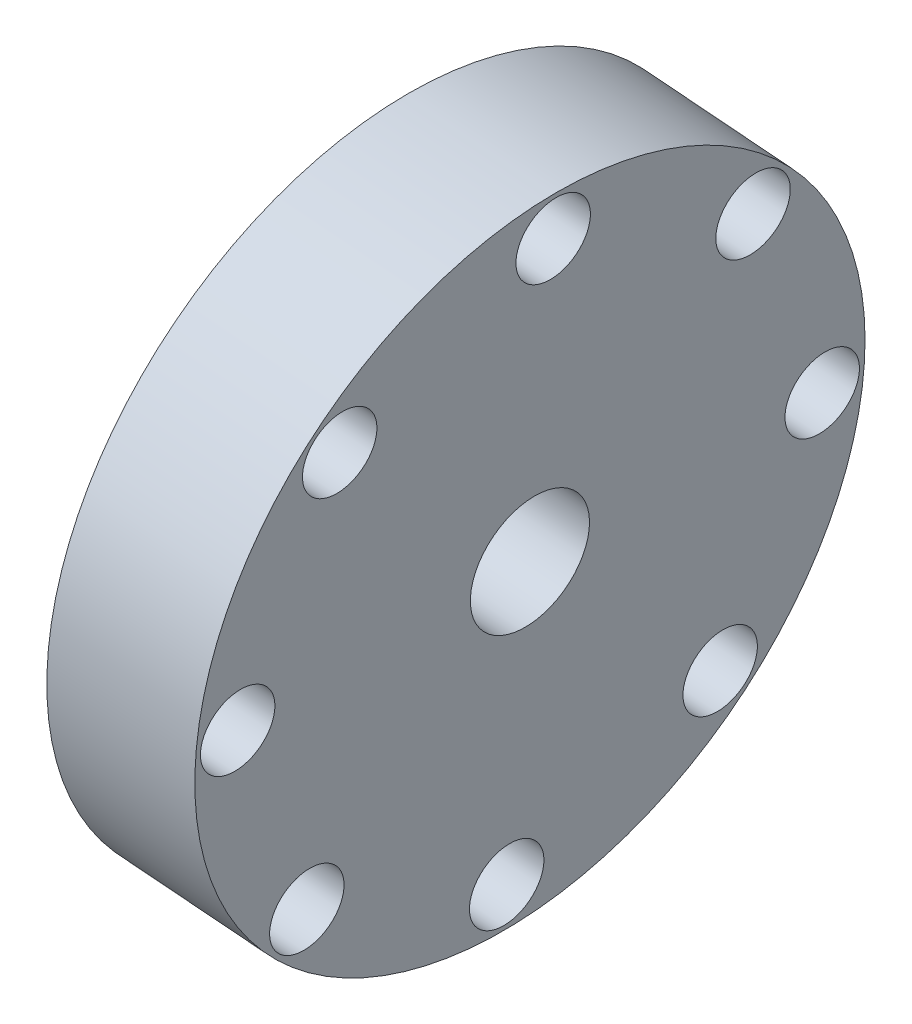
SolidWorks part; units mm, degrees
ref_plane "Front Plane" through (0, 0, 0) normal (0, 0, 1) x (1, 0, 0)
ref_plane "Top Plane" through (0, 0, 0) normal (0, 1, 0) x (1, 0, 0)
ref_plane "Right Plane" through (0, 0, 0) normal (1, 0, 0) x (0, 0, -1)
sketch "Sketch1" plane through (234.2789, -18.689, 0) normal (0.9968, -0.0795, 0) x (0, 0, -1)
  circle A1 centre (-43.1743, 8.5503) radius 14.2875
  dimension "D1" = 28.575
extrude "Boss-Extrude1" add sketch "Sketch1" against normal blind 6.35
sketch "Sketch2" plane through (234.2789, -18.689, 0) normal (0.9968, -0.0795, 0) x (0, 0, -1)
  circle A0 centre (-43.1743, 8.5503) radius 2.54
extrude "Cut-Extrude1" cut sketch "Sketch2" against normal blind 5.08
sketch "Sketch3" plane through (227.949, -18.1841, 0) normal (-0.9968, 0.0795, 0) x (0, 0, 1)
  circle A0 centre (43.1743, 21.0503) radius 1.5875
  circle A1 centre (43.1743, 8.5503) radius 14.2875 construction
  circle A2 centre (43.1743, 8.5503) radius 14.2875
  circle A3 centre (52.0131, 17.3892) radius 1.5875
  circle A4 centre (55.6743, 8.5503) radius 1.5875
  circle A5 centre (52.0131, -0.2885) radius 1.5875
  circle A6 centre (43.1743, -3.9497) radius 1.5875
  circle A7 centre (34.3354, -0.2885) radius 1.5875
  circle A8 centre (30.6743, 8.5503) radius 1.5875
  circle A9 centre (34.3354, 17.3892) radius 1.5875
  point P21 (43.1743, 8.5503)
  dimension "D1" = 3.175
  dimension "D3" = 12.5
  dimension "D2" = 8
extrude "Cut-Extrude2" cut sketch "Sketch3" against normal blind 10 contours A8 | A0 | A3 | A4 | A5 | A6 | A7 | A9 region at (229.6229, 2.7996, 43.1743) region at (229.3318, -0.85, 52.0131) region at (228.6289, -9.6608, 55.6743) region at (227.926, -18.4717, 52.0131) region at (227.6349, -22.1212, 43.1743) region at (227.926, -18.4717, 34.3354) region at (228.6289, -9.6608, 30.6743)
sketch "Sketch4" plane through (234.2789, -18.689, 0) normal (0.9968, -0.0795, 0) x (0, 0, -1)
  line L0 (-57.4618, 8.5503) -> (-28.8868, 8.5503) construction
  circle A0 centre (-43.1743, 8.5503) radius 14.2875 construction
